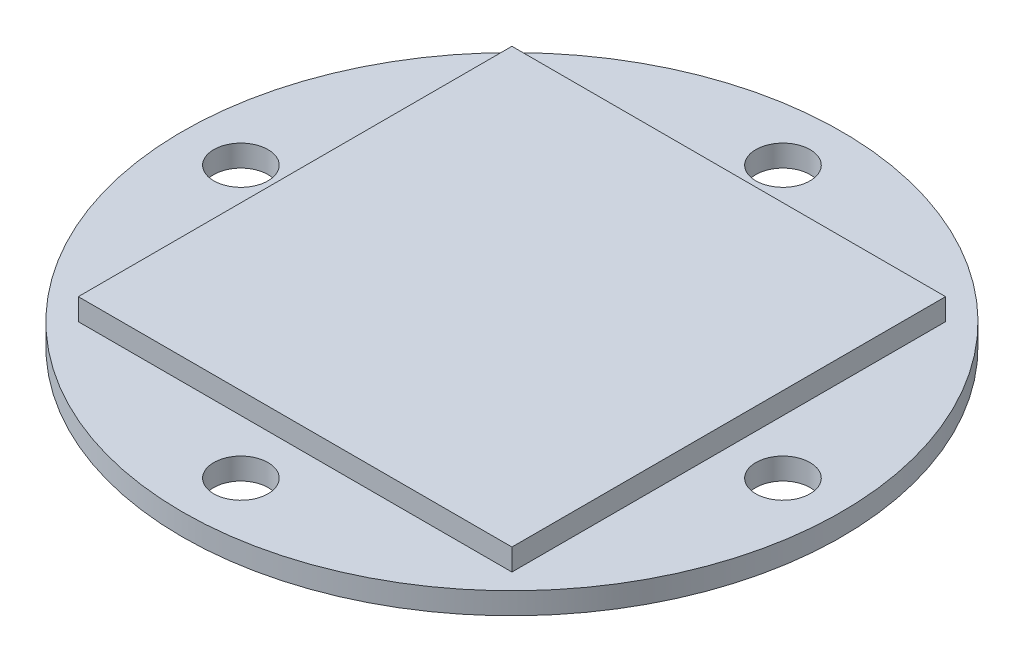
SolidWorks part; units mm, degrees
material "Custom Plastic"
ref_plane "Front Plane" through (0, 0, 0) normal (0, 0, 1) x (1, 0, 0)
ref_plane "Top Plane" through (0, 0, 0) normal (0, 1, 0) x (1, 0, 0)
ref_plane "Right Plane" through (0, 0, 0) normal (1, 0, 0) x (0, 0, -1)
sketch "Sketch1" plane through (0, 0, 0) normal (0, 1, 0) x (1, 0, 0)
  circle A0 centre (0, 0) radius 76
  circle A1 centre (0, 0) radius 62.5 construction
  circle A2 centre (62.5, 0) radius 6.25
  circle A3 centre (0, 62.5) radius 6.25
  circle A4 centre (-62.5, 0) radius 6.25
  circle A5 centre (0, -62.5) radius 6.25
  dimension "D1" = 12.5
  dimension "D2" = 152
  dimension "D3" = 125
extrude "Boss-Extrude1" add sketch "Sketch1" along normal blind 5 contours A0 | A4 | A4 | A3 | A3 | A2 | A2 | A5 | A5 region at (0, 0, 0) region at (62.5, 0, 0) region at (0, 0, -62.5) region at (-62.5, 0, 0) region at (0, 0, 62.5)
extrude "Cut-Extrude2" cut sketch "Sketch1<5>" along normal blind 5 contours A4 | A3 | A2 | A5 region at (62.5, 0, 0) region at (0, 0, -62.5) region at (-62.5, 0, 0)
sketch "Sketch1<5>" plane through (0, 0, 0) normal (0, 1, 0) x (1, 0, 0) same geometry as "Sketch1"
sketch "Sketch2" plane through (0, 5, 0) normal (0, 1, 0) x (1, 0, 0)
  line L1 (-50, 50) -> (50, 50)
  line L2 (-50, 50) -> (-50, -50)
  line L3 (-50, -50) -> (50, -50)
  line L4 (50, 50) -> (50, -50)
  line L5 (-50, 50) -> (50, -50) construction
  line L6 (-50, -50) -> (50, 50) construction
  point P0 (0, 0)
  dimension "D1" = 100
  dimension "D2" = 100
extrude "Boss-Extrude2" add sketch "Sketch2" along normal blind 5 contours L2 L1 L4 L3
sketch "Sketch3" plane through (0, 0, 0) normal (0, -1, 0) x (1, 0, 0)
  line L0 (0, 0) -> (114.2389, 0) construction
  line L1 (0, 0) -> (0, 84.4662) construction
  line L3 (7.5, -20) -> (-7.5, -20)
  line L4 (7.5, -20) -> (7.5, 20)
  line L5 (7.5, 20) -> (-7.5, 20)
  line L6 (-7.5, -20) -> (-7.5, 20)
  line L7 (7.5, -20) -> (-7.5, 20) construction
  line L8 (7.5, 20) -> (-7.5, -20) construction
  line L9 (7.5, 20) -> (22.5, 20)
  line L10 (7.5, 20) -> (7.5, -20)
  line L11 (7.5, -20) -> (22.5, -20)
  line L12 (22.5, 20) -> (22.5, -20)
  line L13 (-7.5, 20) -> (-22.5, 20)
  line L14 (-7.5, 20) -> (-7.5, -20)
  line L15 (-7.5, -20) -> (-22.5, -20)
  line L16 (-22.5, 20) -> (-22.5, -20)
  point P1 (0, 0)
  dimension "D1" = 40
  dimension "D2" = 15
  dimension "D3" = 15
  dimension "D4" = 15
extrude "Boss-Extrude3" add sketch "Sketch3" along normal blind 35 contours L13 L16 L15 L6 | L12 L9 L4 L11 region at (15, 0, 0) region at (-15, 0, 0)
fillet "Fillet3" radius 20 4 edges at (15, -35, -20) (15, -35, 20) (-15, -35, 20) (-15, -35, -20)
sketch "Sketch5" plane through (22.5, 0, 0) normal (1, 0, 0) x (0, 0, -1)
  line L3 (20, -15) -> (20, 0)
  line L4 (20, 0) -> (-20, 0)
  line L5 (-20, 0) -> (-20, -15)
  line L10 (20, 0) -> (-20, 0)
  circle A0 centre (0, -15) radius 10
  arc A6 (-20, -15) -> (0, -35) centre (0, -15) ccw
  arc A7 (0, -35) -> (20, -15) centre (0, -15) ccw
  point P1 (0, 0)
  point P4 (0, 0)
  dimension "D2" = 20
  dimension "D3" = 15
  dimension "D1" = 0
extrude "Cut-Extrude3" cut sketch "Sketch5" against normal blind 72 contours A0 region at (22.5, -15, 0)
